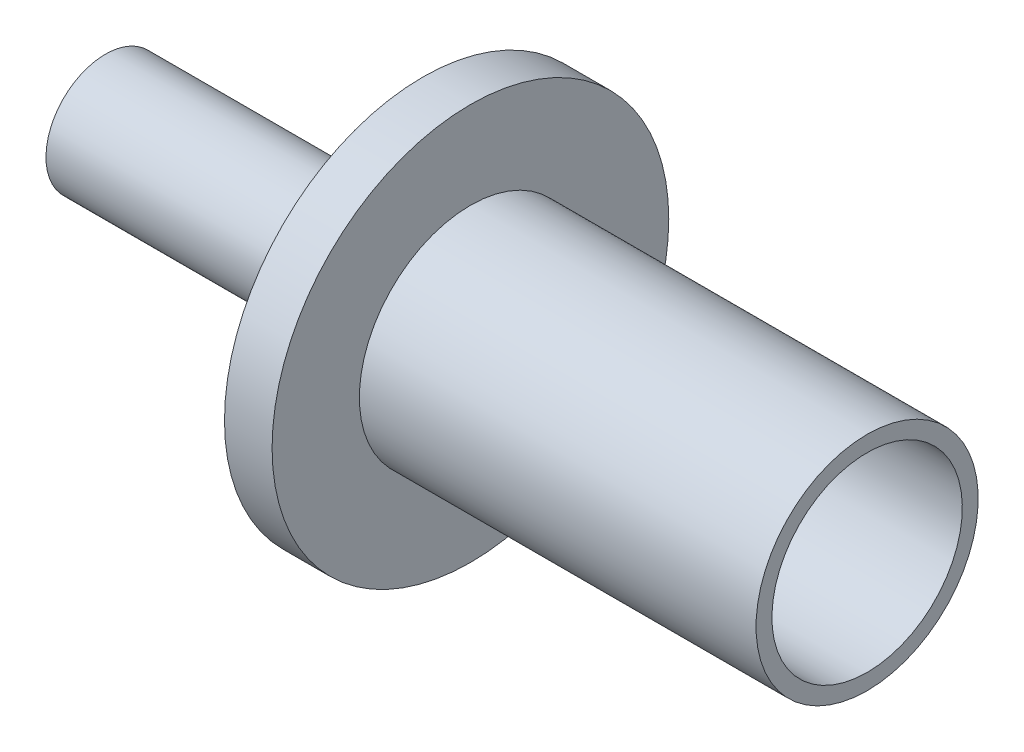
SolidWorks part; units mm, degrees
ref_plane "Front Plane" through (0, 0, 0) normal (0, 0, 1) x (1, 0, 0)
ref_plane "Top Plane" through (0, 0, 0) normal (0, 1, 0) x (1, 0, 0)
ref_plane "Right Plane" through (0, 0, 0) normal (1, 0, 0) x (0, 0, -1)
sketch "Sketch2" plane through (0, 0, 0) normal (0, 0, 1) x (1, 0, 0)
  line L0 (-53.0183, 0) -> (53.0183, 0) construction
  line L1 (0, -40.0686) -> (0, 40.0686) construction
sketch "Sketch1" plane through (0, 0, 0) normal (0, 0, 1) x (1, 0, 0)
  line L0 (-64.9001, 0) -> (64.9001, 0) construction
  line L1 (0, 25) -> (0, 7.5)
  line L4 (19, 12) -> (56, 12)
  line L5 (56, 12) -> (56, 14)
  line L6 (56, 14) -> (6, 14)
  line L7 (6, 14) -> (6, 25)
  line L8 (6, 25) -> (0, 25)
  line L10 (19, 6.5) -> (-40, 6.5)
  line L11 (-40, 6.5) -> (-40, 7.5)
  line L12 (-40, 7.5) -> (0, 7.5)
  line L15 (19, 12) -> (19, 6.5)
  point P3 (0, 0)
  point P6 (3, 25)
  dimension "D1" = 24
  dimension "D2" = 28
  dimension "D3" = 13
  dimension "D4" = 50
  dimension "D5" = 6
  dimension "D6" = 50
  dimension "D7" = 15
  dimension "D8" = 40
  dimension "D9" = 13
revolve "Revolve1" add sketch "Sketch1" angle 360 about L0
sketch "Sketch4" plane through (0, 0, 0) normal (0, 1, 0) x (1, 0, 0)
  line L0 (-53.0183, 0) -> (53.0183, 0) construction
  line L1 (19, -6.5) -> (11, -6.5)
  line L2 (19, -6.5) -> (19, 6.5)
  line L3 (19, 6.5) -> (11, 6.5)
  line L4 (11, -6.5) -> (11, 6.5)
  line L6 (-9.6, 6.5) -> (-5, 6.5)
  line L7 (-9.6, 6.5) -> (-9.6, -6.5)
  line L8 (-9.6, -6.5) -> (-5, -6.5)
  line L9 (-5, 6.5) -> (-5, -6.5)
  line L10 (-9.6, 6.5) -> (-5, -6.5) construction
  line L11 (-9.6, -6.5) -> (-5, 6.5) construction
  point P4 (11, 0)
  point P8 (-7.3, 0)
  dimension "D1" = 8
  dimension "D2" = 13
  dimension "D3" = 5
  dimension "D4" = 13
  dimension "D5" = 4.6
extrude "Cut-Extrude1" cut sketch "Sketch4" against normal up to next contours L4 L1 L2 L3 region at (15, 0, 0)
extrude "Cut-Extrude2" cut sketch "Sketch4<3>" along normal up to next contours L9 L6 L7 L8 region at (-7.3, 0, 0)
sketch "Sketch4<3>" plane through (0, 0, 0) normal (0, 1, 0) x (1, 0, 0) same geometry as "Sketch4"
